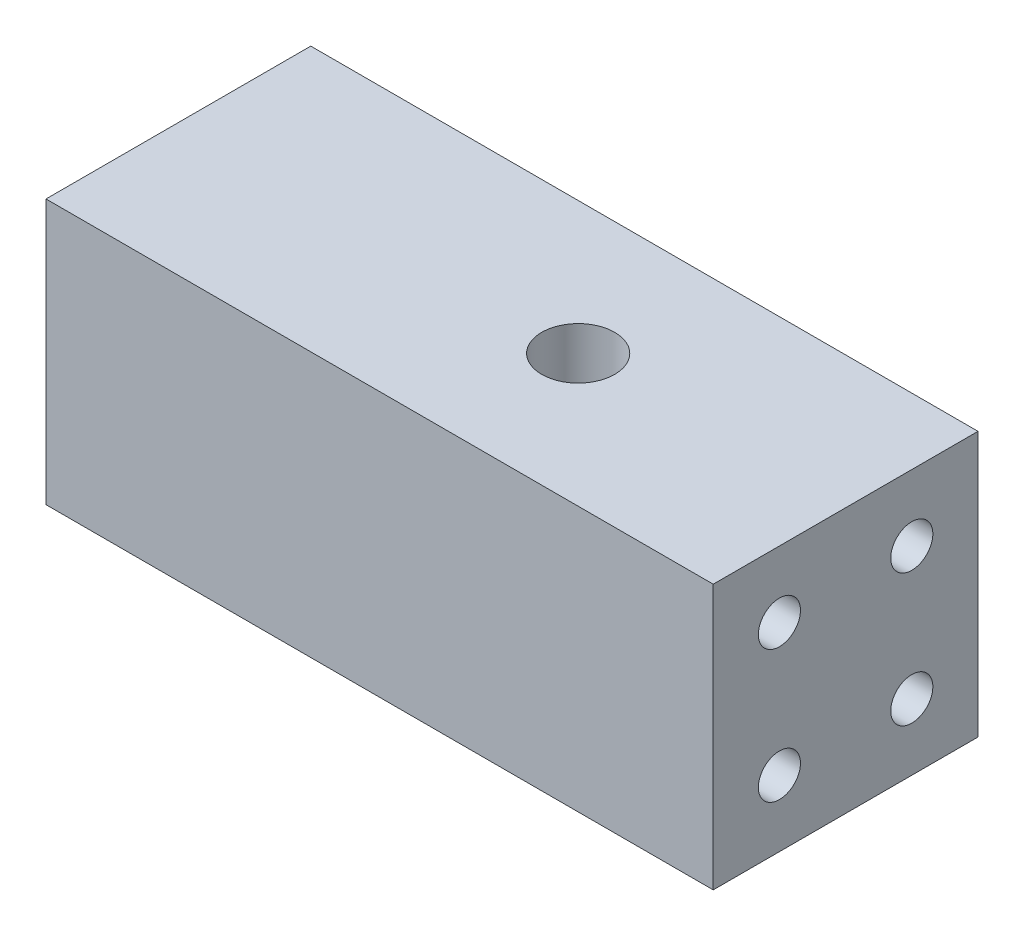
SolidWorks part; units mm, degrees
material "6061-T6 (SS)"
ref_plane "Front Plane" through (0, 0, 0) normal (0, 0, 1) x (1, 0, 0)
ref_plane "Top Plane" through (0, 0, 0) normal (0, 1, 0) x (1, 0, 0)
ref_plane "Right Plane" through (0, 0, 0) normal (1, 0, 0) x (0, 0, -1)
sketch "Sketch1" plane through (0, 0, 0) normal (0, 1, 0) x (1, 0, 0)
  line L1 (0, 0) -> (64.008, 0)
  line L2 (0, 0) -> (0, 25.4)
  line L3 (0, 25.4) -> (64.008, 25.4)
  line L4 (64.008, 0) -> (64.008, 25.4)
  dimension "D1" = 25.4
  dimension "D2" = 64.008
extrude "Boss-Extrude1" add sketch "Sketch1" along normal blind 25.4
hole_wizard "#10-32 Tapped Hole1" positions "Sketch2" profile "Sketch3" tap size "#10-32" standard "ANSI Inch"
sketch "Sketch2" plane through (64.008, 0, 0) normal (1, 0, 0) x (0, 0, -1)
  point P0 (6.35, 19.05)
  point P2 (19.05, 19.05)
  point P4 (19.05, 6.35)
  point P6 (6.35, 6.35)
  dimension "D1" = 6.35
  dimension "D2" = 6.35
  dimension "D3" = 6.35
  dimension "D4" = 6.35
  dimension "D5" = 6.35
  dimension "D6" = 6.35
  dimension "D7" = 6.35
  dimension "D8" = 6.35
sketch "Sketch3" plane through (64.008, 19.05, -6.35) normal (0, 1, 0) x (0, 0, -1)
  line L0 (0, 0) -> (0, 9.8493)
  line L1 (0, 9.8493) -> (2.0193, 8.636)
  line L2 (2.0193, 8.636) -> (2.0193, 0)
  line L5 (2.0193, 0) -> (0, 0)
  line L10 (0, 9.8493) -> (-2.0193, 8.636) construction
  line L11 (0, -6.35) -> (0, 107.95) construction
  dimension "Tap Drill Dia." = 4.0386
  dimension "Tap Drill Depth" = 8.636
  dimension "Drill Angle" = 118
cosmetic thread "Hole Thread1" parameters "D1"=6.35, "D2"=4.826
cosmetic thread "Hole Thread2" parameters "D1"=6.35, "D2"=4.826
cosmetic thread "Hole Thread3" parameters "D1"=6.35, "D2"=4.826
cosmetic thread "Hole Thread4" parameters "D1"=6.35, "D2"=4.826
hole_wizard "#10-32 Tapped Hole2" positions "Sketch4" profile "Sketch5" tap size "#10-32" standard "ANSI Inch"
sketch "Sketch4" plane through (0, 0, 0) normal (-1, 0, 0) x (0, 0, 1)
  point P0 (-19.05, 19.05)
  point P2 (-6.35, 19.05)
  point P4 (-6.35, 6.35)
  point P6 (-19.05, 6.35)
  dimension "D1" = 6.35
  dimension "D2" = 6.35
  dimension "D3" = 6.35
  dimension "D4" = 6.35
  dimension "D5" = 6.35
  dimension "D6" = 6.35
  dimension "D7" = 6.35
  dimension "D8" = 6.35
sketch "Sketch5" plane through (0, 19.05, -19.05) normal (0, 1, 0) x (0, 0, 1)
  line L0 (0, 0) -> (0, 9.8493)
  line L1 (0, 9.8493) -> (2.0193, 8.636)
  line L2 (2.0193, 8.636) -> (2.0193, 0)
  line L5 (2.0193, 0) -> (0, 0)
  line L10 (0, 9.8493) -> (-2.0193, 8.636) construction
  line L11 (0, -6.35) -> (0, 107.95) construction
  dimension "Tap Drill Dia." = 4.0386
  dimension "Tap Drill Depth" = 8.636
  dimension "Drill Angle" = 118
cosmetic thread "Hole Thread5" parameters "D1"=6.35, "D2"=4.826
cosmetic thread "Hole Thread6" parameters "D1"=6.35, "D2"=4.826
cosmetic thread "Hole Thread7" parameters "D1"=6.35, "D2"=4.826
cosmetic thread "Hole Thread8" parameters "D1"=6.35, "D2"=4.826
hole_wizard "Ø6.0mm Dowel Hole1" positions "Sketch7" profile "Sketch9" hole size "Ø6.0" standard "ANSI Metric" end condition through all
sketch "Sketch7" plane through (0, 25.4, 0) normal (0, 1, 0) x (1, 0, 0)
  point P0 (38.354, 12.7)
  dimension "D1" = 12.7
  dimension "D2" = 38.354
sketch "Sketch9" plane through (38.354, 25.4, -12.7) normal (1, 0, 0) x (0, 0, 1)
  line L0 (0, 0) -> (0, 25.4)
  line L1 (0, 25.4) -> (3.5, 25.4)
  line L2 (3.5, 25.4) -> (3.5, 0)
  line L5 (3.5, 0) -> (0, 0)
  line L11 (0, -6.35) -> (0, 107.95) construction
  dimension "Thru Hole Dia." = 7
  dimension "Thru Hole Depth" = 25.4
